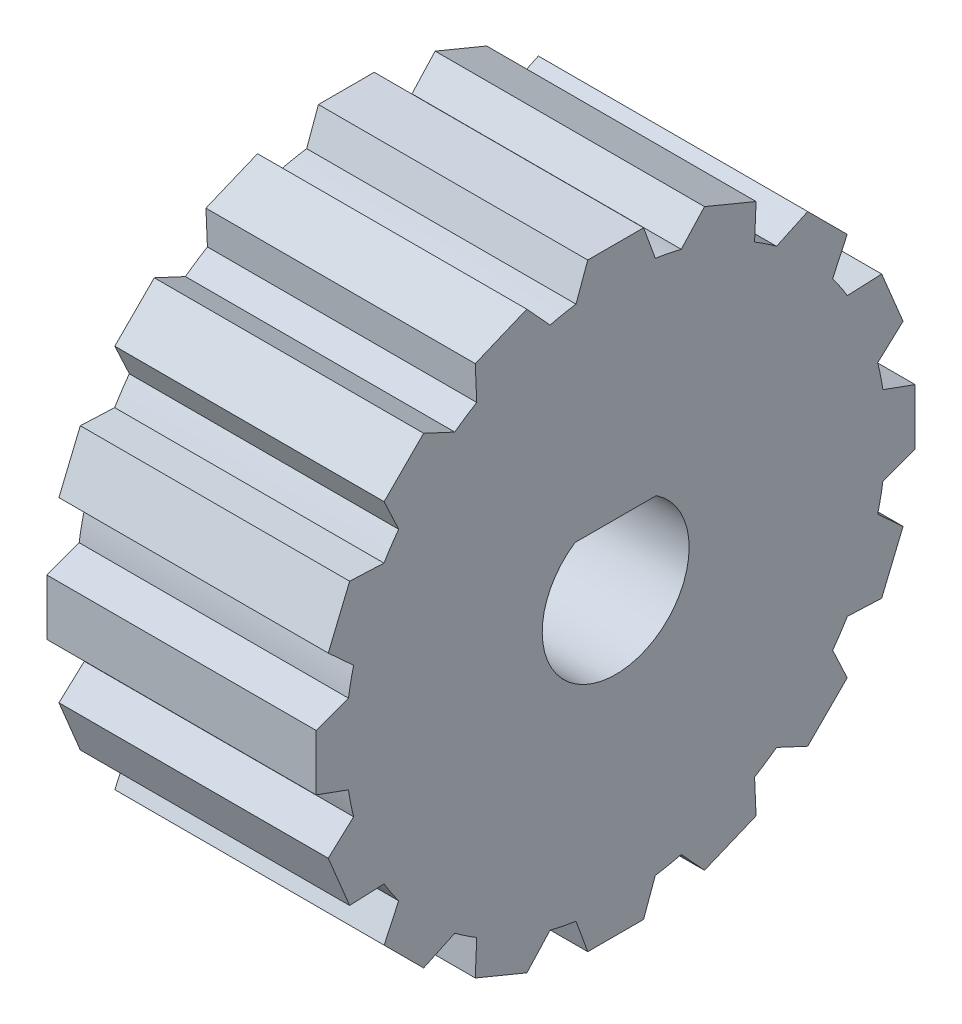
SolidWorks part; units mm, degrees
ref_plane "Front Plane" through (0, 0, 0) normal (0, 0, 1) x (1, 0, 0)
ref_plane "Top Plane" through (0, 0, 0) normal (0, 1, 0) x (1, 0, 0)
ref_plane "Right Plane" through (0, 0, 0) normal (1, 0, 0) x (0, 0, -1)
sketch "Sketch1" plane through (0, 0, 0) normal (0, 0, 1) x (1, 0, 0)
  line L0 (-7.5, 12.3) -> (-7.5, 0)
  line L1 (-7.5, 0) -> (7.5, 0)
  line L2 (7.5, 0) -> (7.5, 12.3)
  line L3 (7.5, 12.3) -> (8.5, 15.5)
  line L4 (8.5, 15.5) -> (7.5, 16)
  line L5 (7.5, 16) -> (6.5, 12.3)
  line L6 (6.5, 12.3) -> (6.5, 11.0324)
  line L7 (6.5, 11.0324) -> (-6.5, 11.0324)
  line L8 (-6.5, 11.0324) -> (-6.5, 12.3)
  line L9 (-6.5, 12.3) -> (-7.5, 16)
  line L10 (-7.5, 16) -> (-8.5, 15.5)
  line L11 (-8.5, 15.5) -> (-7.5, 12.3)
  line L12 (-8.5, 0) -> (8.5, 0) construction
revolve "Revolve1" add sketch "Sketch1" angle 360 about L12 reverse direction yes
sketch "Sketch2" plane through (7.5, 0, 0) normal (1, 0, 0) x (0, 0, -1)
  circle A0 centre (0, 0) radius 9
sketch "Sketch5" plane through (0, 0, 0) normal (0, 0, 1) x (1, 0, 0)
  line L0 (-6.5, -12.2324) -> (6.5, -12.2324)
rib "Rib1" sketch "Sketch5" sketch "Sketch5" thickness 2.2803 extrusion direction parallel to sketch draft on yes draft angle 20 parameters "D1"=2.2803, "D3"=20
ref_plane "Plane1" through (0, 0, 0) normal (0, -1, 0) x (1, 0, 0)
sketch "Sketch6" plane through (0, 0, 0) normal (0, -1, 0) x (1, 0, 0)
  line L0 (-6.5, -12.2324) -> (6.5, -12.2324)
rib "Rib2" sketch "Sketch6" sketch "Sketch6" thickness 2.2803 extrusion direction parallel to sketch draft on yes draft angle 20 parameters "D1"=2.2803, "D3"=20
ref_plane "Plane2" through (0, 0, 0) normal (0, 0, -1) x (-1, 0, 0)
sketch "Sketch7" plane through (0, 0, 0) normal (0, 0, -1) x (-1, 0, 0)
  line L0 (6.5, 12.2324) -> (-6.5, 12.2324)
rib "Rib3" sketch "Sketch7" sketch "Sketch7" thickness 2.2803 extrusion direction parallel to sketch draft on yes draft angle 20 parameters "D1"=2.2803, "D3"=20
sketch "Sketch8" plane through (0, 0, 0) normal (0, 1, 0) x (1, 0, 0)
  line L0 (-6.5, -12.2324) -> (6.5, -12.2324)
rib "Rib4" sketch "Sketch8" sketch "Sketch8" thickness 2.2803 extrusion direction parallel to sketch draft on yes draft angle 20 parameters "D1"=2.2803, "D3"=20
ref_plane "Plane3" through (0, 0, 0) normal (0, 0.7071, -0.7071) x (-1, 0, 0)
sketch "Sketch9" plane through (0, 0, 0) normal (0, 0.7071, -0.7071) x (-1, 0, 0)
  line L0 (6.5, 12.2324) -> (-6.5, 12.2324)
rib "Rib5" sketch "Sketch9" sketch "Sketch9" thickness 2.2803 extrusion direction parallel to sketch draft on yes draft angle 20 parameters "D1"=2.2803, "D3"=20
ref_plane "Plane4" through (0, 0, 0) normal (0, 0.3827, -0.9239) x (-1, 0, 0)
sketch "Sketch10" plane through (0, 0, 0) normal (0, 0.3827, -0.9239) x (-1, 0, 0)
  line L0 (6.5, 12.2324) -> (-6.5, 12.2324)
rib "Rib6" sketch "Sketch10" sketch "Sketch10" thickness 2.2803 extrusion direction parallel to sketch draft on yes draft angle 20 parameters "D1"=2.2803, "D3"=20
ref_plane "Plane5" through (0, 0, 0) normal (0, -0.9239, -0.3827) x (1, 0, 0)
sketch "Sketch11" plane through (0, 0, 0) normal (0, -0.9239, -0.3827) x (1, 0, 0)
  line L0 (-6.5, -12.2324) -> (6.5, -12.2324)
rib "Rib7" sketch "Sketch11" sketch "Sketch11" thickness 2.2803 extrusion direction parallel to sketch draft on yes draft angle 20 parameters "D1"=2.2803, "D3"=20
ref_plane "Plane6" through (0, 0, 0) normal (0, 0.9239, -0.3827) x (-1, 0, 0)
sketch "Sketch12" plane through (0, 0, 0) normal (0, 0.9239, -0.3827) x (-1, 0, 0)
  line L0 (6.5, 12.2324) -> (-6.5, 12.2324)
rib "Rib8" sketch "Sketch12" sketch "Sketch12" thickness 2.2803 extrusion direction parallel to sketch draft on yes draft angle 20 parameters "D1"=2.2803, "D3"=20
ref_plane "Plane7" through (0, 0, 0) normal (0, 0.7071, 0.7071) x (-1, 0, 0)
sketch "Sketch13" plane through (0, 0, 0) normal (0, 0.7071, 0.7071) x (-1, 0, 0)
  line L0 (6.5, 12.2324) -> (-6.5, 12.2324)
rib "Rib9" sketch "Sketch13" sketch "Sketch13" thickness 2.2803 extrusion direction parallel to sketch draft on yes draft angle 20 parameters "D1"=2.2803, "D3"=20
ref_plane "Plane8" through (0, 0, 0) normal (0, -0.7071, -0.7071) x (1, 0, 0)
sketch "Sketch14" plane through (0, 0, 0) normal (0, -0.7071, -0.7071) x (1, 0, 0)
  line L0 (-6.5, -12.2324) -> (6.5, -12.2324)
rib "Rib10" sketch "Sketch14" sketch "Sketch14" thickness 2.2803 extrusion direction parallel to sketch draft on yes draft angle 20 parameters "D1"=2.2803, "D3"=20
ref_plane "Plane9" through (0, 0, 0) normal (0, -0.7071, 0.7071) x (1, 0, 0)
sketch "Sketch15" plane through (0, 0, 0) normal (0, -0.7071, 0.7071) x (1, 0, 0)
  line L0 (-6.5, -12.2324) -> (6.5, -12.2324)
rib "Rib11" sketch "Sketch15" sketch "Sketch15" thickness 2.2803 extrusion direction parallel to sketch draft on yes draft angle 20 parameters "D1"=2.2803, "D3"=20
ref_plane "Plane10" through (0, 0, 0) normal (0, -0.3827, -0.9239) x (1, 0, 0)
sketch "Sketch16" plane through (0, 0, 0) normal (0, -0.3827, -0.9239) x (1, 0, 0)
  line L0 (-6.5, -12.2324) -> (6.5, -12.2324)
rib "Rib12" sketch "Sketch16" sketch "Sketch16" thickness 2.2803 extrusion direction parallel to sketch draft on yes draft angle 20 parameters "D1"=2.2803, "D3"=20
ref_plane "Plane11" through (0, 0, 0) normal (0, -0.3827, 0.9239) x (1, 0, 0)
sketch "Sketch17" plane through (0, 0, 0) normal (0, -0.3827, 0.9239) x (1, 0, 0)
  line L0 (-6.5, -12.2324) -> (6.5, -12.2324)
rib "Rib13" sketch "Sketch17" sketch "Sketch17" thickness 2.2803 extrusion direction parallel to sketch draft on yes draft angle 20 parameters "D1"=2.2803, "D3"=20
ref_plane "Plane12" through (0, 0, 0) normal (0, 0.9239, 0.3827) x (-1, 0, 0)
sketch "Sketch18" plane through (0, 0, 0) normal (0, 0.9239, 0.3827) x (-1, 0, 0)
  line L0 (6.5, 12.2324) -> (-6.5, 12.2324)
rib "Rib14" sketch "Sketch18" sketch "Sketch18" thickness 2.2803 extrusion direction parallel to sketch draft on yes draft angle 20 parameters "D1"=2.2803, "D3"=20
ref_plane "Plane13" through (0, 0, 0) normal (0, -0.9239, 0.3827) x (1, 0, 0)
sketch "Sketch19" plane through (0, 0, 0) normal (0, -0.9239, 0.3827) x (1, 0, 0)
  line L0 (-6.5, -12.2324) -> (6.5, -12.2324)
rib "Rib15" sketch "Sketch19" sketch "Sketch19" thickness 2.2803 extrusion direction parallel to sketch draft on yes draft angle 20 parameters "D1"=2.2803, "D3"=20
ref_plane "Plane14" through (0, 0, 0) normal (0, 0.3827, 0.9239) x (-1, 0, 0)
sketch "Sketch20" plane through (0, 0, 0) normal (0, 0.3827, 0.9239) x (-1, 0, 0)
  line L0 (6.5, 12.2324) -> (-6.5, 12.2324)
rib "Rib16" sketch "Sketch20" sketch "Sketch20" thickness 2.2803 extrusion direction parallel to sketch draft on yes draft angle 20 parameters "D1"=2.2803, "D3"=20
sketch "Sketch22" plane through (7.5, 0, 0) normal (1, 0, 0) x (0, 0, -1)
  circle A0 centre (0, 0) radius 1.5
  dimension "D1" = 3
extrude "Cut-Extrude3" cut sketch "Sketch22" against normal through all
sketch "Sketch21" plane through (-6.5, 0, 0) normal (1, 0, 0) x (0, 0, -1)
  circle A0 centre (0, 0) radius 20.0004
extrude "Cut-Extrude1" cut sketch "Sketch21" against normal through all
extrude "Cut-Extrude2" cut sketch "Sketch21<2>" along normal through all from surface starting at face at (6.5, 0, -12.3)
sketch "Sketch21<2>" plane through (-6.5, 0, 0) normal (1, 0, 0) x (0, 0, -1) same geometry as "Sketch21"
sketch "Sketch23" plane through (6.5, 0, 0) normal (1, 0, 0) x (0, 0, -1)
  line L0 (-1.6583, 2.5) -> (1.6583, 2.5)
  circle A0 centre (0, 0) radius 3 construction
  circle A1 centre (0, 0) radius 2.5 construction
  arc A2 (-1.6583, 2.5) -> (1.6583, 2.5) centre (0, 0) ccw
  dimension "D1" = 5
  dimension "D2" = 6
extrude "Cut-Extrude4" cut sketch "Sketch23" against normal through all
sketch "Sketch24" plane through (6.5, 0, 0) normal (1, 0, 0) x (0, 0, -1)
  circle A0 centre (0, 0) radius 18.9616
extrude "Cut-Extrude5" cut sketch "Sketch24" against normal blind 2
